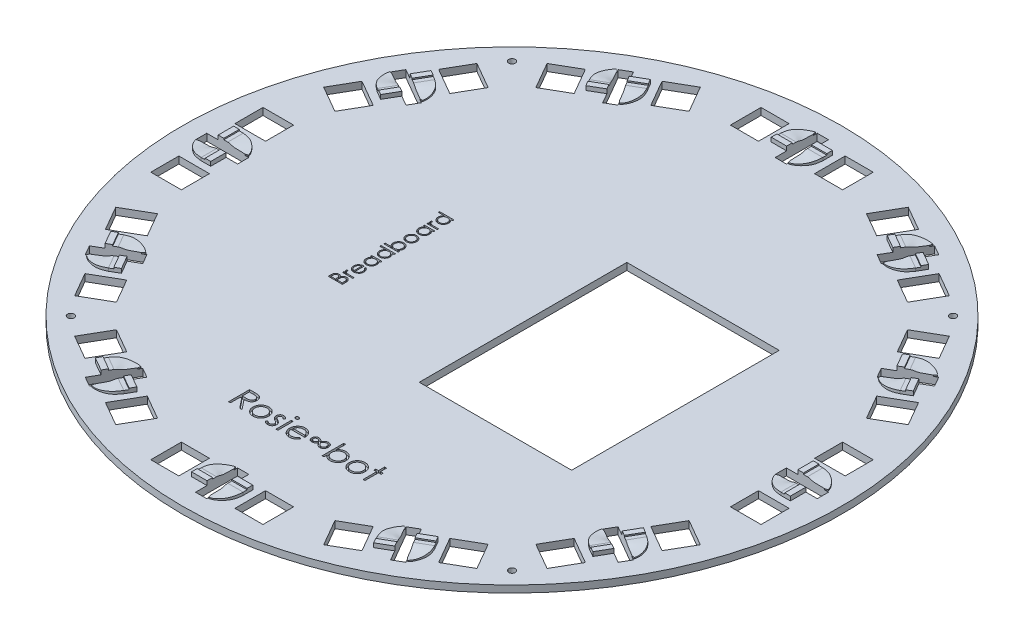
SolidWorks part; units mm, degrees
ref_plane "Front" through (0, 0, 0) normal (0, 0, 1) x (1, 0, 0)
ref_plane "Top" through (0, 0, 0) normal (0, 1, 0) x (1, 0, 0)
ref_plane "Right" through (0, 0, 0) normal (1, 0, 0) x (0, 0, -1)
sketch "Sketch1" plane through (0, 0, 0) normal (0, 1, 0) x (1, 0, 0)
  circle A0 centre (0, 0) radius 149.225
  dimension "D1" = 298.45
extrude "Base" add sketch "Sketch1" along normal blind 3.175 contours A0
sketch "Sketch2" plane through (0, 3.175, 0) normal (0, 1, 0) x (1, 0, 0)
  line L1 (-2.54, -140.758) -> (2.54, -140.758)
  line L2 (-2.54, -140.758) -> (-2.54, -121.708)
  line L3 (-2.54, -121.708) -> (2.54, -121.708)
  line L4 (2.54, -140.758) -> (2.54, -121.708)
  circle A0 centre (0, 0) radius 149.225 construction
  point P4 (0, -121.708)
  dimension "D1" = 5.08
  dimension "D2" = 19.05
  dimension "D3" = 140.758
extrude "Cut-Extrude1" cut sketch "Sketch2" against normal up to next and the other way through all contours L1 L4 L3 L2
sketch "Sketch4" plane through (0, 3.175, 0) normal (0, 1, 0) x (1, 0, 0)
  line L0 (0, -131.233) -> (-2.9434, -122.1742) construction
  line L1 (-2.9434, -122.1742) -> (0, -131.233) construction
  line L2 (0, -131.233) -> (-5.5987, -123.5271) construction
  line L3 (0, -131.233) -> (-7.7059, -125.6343) construction
  line L4 (0, -131.233) -> (-9.0588, -128.2896) construction
  line L5 (0, -131.233) -> (-9.525, -131.233) construction
  line L9 (2.54, -121.708) -> (-2.54, -121.708) construction
  line L10 (2.54, -121.708) -> (2.54, -140.758) construction
  line L11 (-2.54, -121.708) -> (-2.54, -140.758) construction
  line L12 (2.54, -140.758) -> (-2.54, -140.758) construction
  circle A0 centre (0, -131.233) radius 9.525 construction
  point P16 (0, -121.708)
  point P19 (2.54, -131.233)
  dimension "D1" = 18
  dimension "D2" = 18
  dimension "D3" = 18
  dimension "D4" = 18
  dimension "D5" = 18
ref_plane "Plane1" through (-38.5684, 0, 12.5316) normal (0.9511, 0, -0.309) x (-0.309, 0, -0.9511)
ref_plane "Plane2" through (-62.405, 0, 45.3399) normal (0.809, 0, -0.5878) x (-0.5878, 0, -0.809)
ref_plane "Plane3" through (-62.405, 0, 85.8931) normal (0.5878, 0, -0.809) x (-0.809, 0, -0.5878)
ref_plane "Plane4" through (-38.5684, 0, 118.7014) normal (0.309, 0, -0.9511) x (-0.9511, 0, -0.309)
ref_plane "Plane5" through (0, 0, 131.233) normal (0, 0, -1) x (-1, 0, 0)
sketch "Sketch5" plane through (-38.5684, 0, 12.5316) normal (0.9511, 0, -0.309) x (-0.309, 0, -0.9511)
  line L0 (-114.9663, 3.175) -> (-133.0839, 3.175) construction
  line L1 (-116.5904, 3.175) -> (-115.285, 3.175)
  line L2 (-116.5904, 3.175) -> (-116.5904, 3.683)
  line L3 (-116.5904, 3.683) -> (-115.285, 3.683)
  line L4 (-115.285, 3.175) -> (-115.285, 3.683)
  dimension "D2" = 0.508
sketch "Sketch6" plane through (-62.405, 0, 45.3399) normal (0.809, 0, -0.5878) x (-0.5878, 0, -0.809)
  line L0 (-96.9709, 3.175) -> (-112.3826, 3.175) construction
  line L1 (-101.8484, 3.175) -> (-96.6447, 3.175)
  line L2 (-101.8484, 3.175) -> (-101.8484, 3.775)
  line L3 (-101.8484, 3.775) -> (-96.6447, 3.775)
  line L4 (-96.6447, 3.175) -> (-96.6447, 3.775)
  dimension "D2" = 0.6
sketch "Sketch7" plane through (-62.405, 0, 85.8931) normal (0.5878, 0, -0.809) x (-0.809, 0, -0.5878)
  line L0 (-69.4833, 3.175) -> (-80.6806, 3.175) construction
  line L1 (-73.9972, 3.175) -> (-67.6118, 3.175)
  line L2 (-73.9972, 3.175) -> (-73.9972, 4.075)
  line L3 (-73.9972, 4.075) -> (-67.6118, 4.075)
  line L4 (-67.6118, 3.175) -> (-67.6118, 4.075)
  dimension "D2" = 0.9
sketch "Sketch10" plane through (-38.5684, 0, 118.7014) normal (0.309, 0, -0.9511) x (-0.9511, 0, -0.309)
  line L0 (-40.5532, 3.175) -> (-31.4944, 3.175) construction
  line L1 (-37.8825, 3.175) -> (-31.0282, 3.175)
  line L2 (-37.8825, 3.175) -> (-37.8825, 4.375)
  line L3 (-37.8825, 4.375) -> (-31.0282, 4.375)
  line L4 (-31.0282, 3.175) -> (-31.0282, 4.375)
  dimension "D3" = 1.2
sketch "Sketch11" plane through (0, 0, 131.233) normal (0, 0, -1) x (-1, 0, 0)
  line L0 (0, 3.175) -> (9.525, 3.175) construction
  line L1 (2.54, 3.175) -> (9.525, 3.175)
  line L2 (2.54, 3.175) -> (2.54, 4.475)
  line L3 (2.54, 4.475) -> (9.525, 4.475)
  line L4 (9.525, 3.175) -> (9.525, 4.475)
  dimension "D3" = 1.3
loft "Loft1" add profiles "Sketch5", "Sketch6", "Sketch7", "Sketch10", "Sketch11" connector at (-2.54, 3.683, 123.4157) connector at (-2.54, 3.775, 127.737) connector at (-2.54, 4.075, 129.3876) connector at (-2.54, 4.375, 130.4077) connector at (-2.54, 4.475, 131.233)
sketch "Sketch13" plane through (-104.9799, 0, 131.233) normal (0, 0, -1) x (-1, 0, 0)
  line L6 (-95.4549, 3.175) -> (-102.4399, 3.175)
  line L7 (-95.4549, 3.175) -> (-95.4549, 4.475)
  line L8 (-95.4549, 4.475) -> (-102.4399, 4.475)
  line L9 (-102.4399, 3.175) -> (-102.4399, 4.475)
extrude "Boss-Extrude4" add sketch "Sketch13" against normal blind 1.7907
sketch "Sketch25" plane through (0, 0, 133.0237) normal (0, 0, 1) x (1, 0, 0)
  line L0 (-9.525, 4.475) -> (-2.54, 4.475) construction
  line L1 (-9.525, 3.175) -> (-2.54, 3.175)
  line L2 (-9.525, 3.175) -> (-9.525, 5.075)
  line L3 (-9.525, 5.075) -> (-2.54, 5.075)
  line L4 (-2.54, 3.175) -> (-2.54, 5.075)
  dimension "D1" = 0.6
extrude "Boss-Extrude5" add sketch "Sketch25" along normal blind 2.54
sketch "Sketch14" plane through (-2.54, 0, 0) normal (1, 0, 0) x (0, 0, -1)
  line L0 (-131.233, 3.175) -> (-131.233, 0) construction
  line L1 (-121.708, 0) -> (-140.758, 0) construction
ref_plane "Plane6" through (0, 0, 0) normal (1, 0, 0) x (0, 0, -1)
sketch "Sketch15" plane through (0, 0, 0) normal (1, 0, 0) x (0, 0, -1)
  line L0 (-131.233, 0) -> (-131.233, 3.175) construction
pattern_circular "CirPattern1" count 2 over 360 about axis through (0, 0, 131.233) along (0, 1, 0) of "Loft1", "Boss-Extrude5", "Boss-Extrude4" reverse direction yes
ref_axis "Axis1" through (0, 50, 0) along (0, -1, 0)
pattern_circular "Full_Spiral_Pattern" count 12 over 360 about axis through (0, 50, 0) along (0, -1, 0) of "CirPattern1", "Cut-Extrude1"
sketch "Sketch19" plane through (0, 3.175, 0) normal (0, 1, 0) x (1, 0, 0)
  line L0 (-99.8612, -99.8612) -> (0, 0) construction
  line L2 (0, 0) -> (0, -149.225) construction
  circle A1 centre (-99.8612, -99.8612) radius 1.5
  circle A2 centre (0, 0) radius 149.225 construction
  dimension "D4" = 3
  dimension "D1" = 141.225
  dimension "D2" = 45
extrude "Cut-Extrude2" cut sketch "Sketch19" against normal through all
pattern_circular "CirPattern7" count 4 over 360 about axis through (0, 50, 0) along (0, -1, 0) of "Cut-Extrude2"
sketch "Sketch23" plane through (0, 3.175, 0) normal (0, 1, 0) x (1, 0, 0)
  line L9 (-2.54, -135.5637) -> (-2.54, -140.758) construction
  line L10 (-25.4, -124.3051) -> (-12.7, -124.3051)
  line L11 (-25.4, -124.3051) -> (-25.4, -138.1608)
  line L16 (-25.4, -138.1608) -> (-12.7, -138.1608)
  line L17 (-12.7, -124.3051) -> (-12.7, -138.1608)
  line L19 (2.54, -121.708) -> (2.54, -126.9023) construction
  line L20 (0, -50) -> (0, 50) construction
  line L21 (12.7, -124.3051) -> (12.7, -138.1608)
  line L22 (25.4, -138.1608) -> (12.7, -138.1608)
  line L23 (25.4, -124.3051) -> (25.4, -138.1608)
  line L24 (25.4, -124.3051) -> (12.7, -124.3051)
  point P8 (-2.54, -138.1608)
  point P9 (2.54, -124.3051)
  dimension "D1" = 12.7
  dimension "D2" = 10.16
extrude "Cut-Extrude6" cut sketch "Sketch23" against normal through all
pattern_circular "CirPattern8" count 12 over 360 about axis through (0, 50, 0) along (0, -1, 0) of "Cut-Extrude6"
sketch "Sketch17" plane through (0, 3.175, 0) normal (0, 1, 0) x (1, 0, 0)
  line L0 (-31.75, -97.8162) -> (31.75, -97.8162) construction
  point P3 (0, -97.8162)
  dimension "D2" = 97.8162
  dimension "D1" = 63.5
sketch "Sketch16" plane through (0, 3.175, 0) normal (0, 1, 0) x (1, 0, 0)
  line L0 (-31.75, -97.8162) -> (31.75, -97.8162) construction
  text T0 "Rosie∞bot\r\n" font "Century Gothic" height in points 36
extrude "Cut-Extrude4" cut sketch "Sketch16" against normal blind 1.27
sketch "Sketch22" plane through (0, 3.175, 0) normal (0, 1, 0) x (1, 0, 0)
  line L0 (-50.8, 25.1735) -> (-50.8, -31.2294) construction
  text T0 "Breadboard"
  dimension "D1" = 50.8
extrude "Cut-Extrude5" cut sketch "Sketch22" against normal blind 1.27
sketch "Sketch27" plane through (0, 3.175, 0) normal (0, 1, 0) x (1, 0, 0)
  line L1 (5, 47) -> (74, 47)
  line L2 (5, 47) -> (5, -47)
  line L3 (5, -47) -> (74, -47)
  line L4 (74, 47) -> (74, -47)
  point P4 (89.5341, 51.8456)
  point P7 (5, 0)
  dimension "D1" = 69
  dimension "D2" = 94
  dimension "D3" = 5
extrude "Cut-Extrude9" cut sketch "Sketch27" against normal through all
equation "\"Diameter_Daisy\"= 11.75in'Outside diameter of base"
equation "\"D1@Sketch1\"=\"Diameter_Daisy\""
equation "\"D3@Sketch2\"=\"Diameter_Daisy\"/2-8.467mm"
equation "\"D1@Sketch19\"=\"Diameter_Daisy\"/2-8mm"
equation "\"Number_of_Holes\" = 12"
equation "\"D1@Full_Spiral_Pattern\"=\"Number_of_Holes\""
equation "\"D1@CirPattern8\"=\"Number_of_Holes\""
